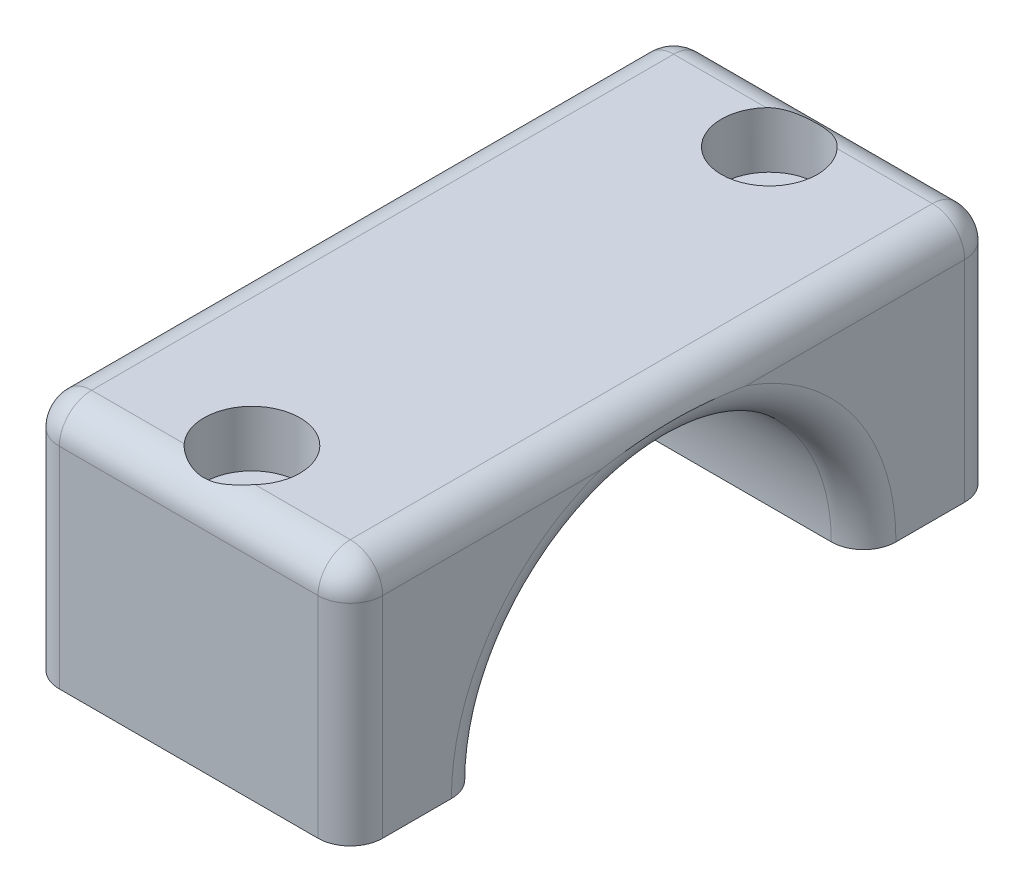
SolidWorks part; units mm, degrees
ref_plane "Front Plane" through (0, 0, 0) normal (0, 0, 1) x (1, 0, 0)
ref_plane "Top Plane" through (0, 0, 0) normal (0, 1, 0) x (1, 0, 0)
ref_plane "Right Plane" through (0, 0, 0) normal (1, 0, 0) x (0, 0, -1)
sketch "Sketch1" plane through (0, 0, 0) normal (1, 0, 0) x (0, 0, -1)
  line L1 (0, 0) -> (50.8, 0)
  line L2 (0, 0) -> (0, 19.05)
  line L3 (0, 19.05) -> (50.8, 19.05)
  line L4 (50.8, 0) -> (50.8, 19.05)
  dimension "D1" = 50.8
  dimension "D2" = 19.05
extrude "Boss-Extrude1" add sketch "Sketch1" along normal blind 25.4
sketch "Sketch2" plane through (25.4, 0, 0) normal (1, 0, 0) x (0, 0, -1)
  line L0 (0, 0) -> (50.8, 0) construction
  circle A0 centre (25.4, 0) radius 14.9225
  dimension "D1" = 29.845
extrude "Cut-Extrude1" cut sketch "Sketch2" against normal through all
hole_wizard "CBORE for #6 Button Head Cap Screw1" positions "Sketch3" profile "Sketch4" counterbore size "#6" standard "ANSI Inch" end condition through all
sketch "Sketch3" plane through (0, 19.05, 0) normal (0, 1, 0) x (1, 0, 0)
  line L0 (0, 25.4) -> (25.4, 25.4) construction
  line L1 (0, 50.8) -> (0, 0) construction
  line L2 (25.4, 50.8) -> (25.4, 0) construction
  line L4 (25.4, 0) -> (0, 0) construction
  point P0 (12.5946, 5.08)
  point P2 (12.5946, 45.72)
  point P17 (0, 0)
  dimension "D1" = 5.08
sketch "Sketch4" plane through (12.5946, 19.05, -5.08) normal (1, 0, 0) x (0, 0, 1)
  line L0 (0, 0) -> (0, 19.05)
  line L1 (0, 19.05) -> (2.1527, 19.05)
  line L3 (2.1527, 19.05) -> (2.1527, 4.3942)
  line L4 (2.1527, 4.3942) -> (3.7706, 4.3942)
  line L5 (3.7706, 4.3942) -> (3.7706, 0)
  line L7 (3.7706, 0) -> (0, 0)
  line L11 (0, -6.35) -> (0, 107.95) construction
  dimension "Thru Hole Dia." = 4.3053
  dimension "Thru Hole Depth" = 19.05
  dimension "C'Bore Dia." = 7.5413
  dimension "C'Bore Depth" = 4.3942
fillet "Fillet1" radius 2.54 10 edges at (12.7, 19.05, -50.8) (25.4, 19.05, -25.4) (12.7, 19.05, 0) (0, 19.05, -25.4) (25.4, 9.525, -50.8) (0, 9.525, -50.8) (25.4, 9.525, 0) (0, 9.525, 0) (25.4, 14.9225, -25.4) (0, 14.9225, -25.4)
